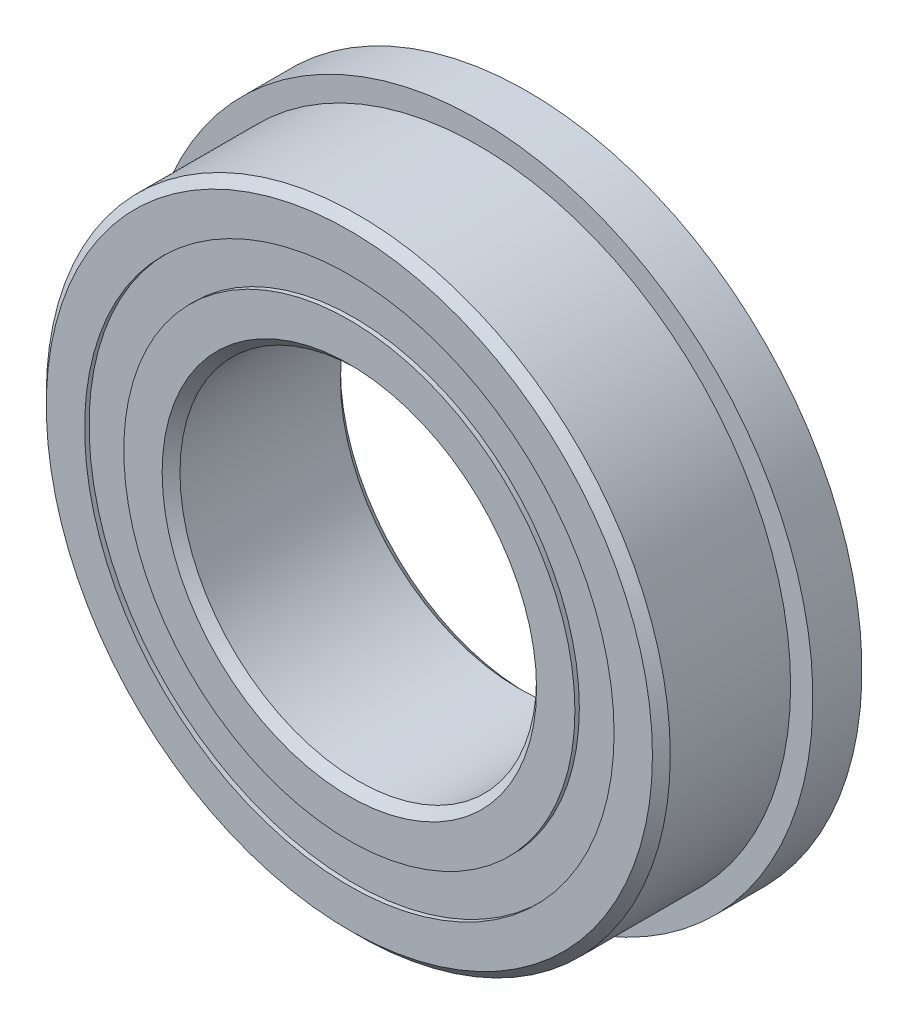
SolidWorks part; units mm, degrees
ref_plane "Front Plane" through (0, 0, 0) normal (0, 0, 1) x (1, 0, 0)
ref_plane "Top Plane" through (0, 0, 0) normal (0, 1, 0) x (1, 0, 0)
ref_plane "Right Plane" through (0, 0, 0) normal (1, 0, 0) x (0, 0, -1)
sketch "Sketch1" plane through (0, 0, 0) normal (1, 0, 0) x (0, 0, -1)
  line L0 (-2, 0) -> (2, 0) construction
  line L1 (0, 7) -> (0, -7) construction
  line L2 (1.8, 7) -> (-1.8, 7)
  line L3 (-1.8, 7) -> (-2, 6.8)
  line L4 (-2, 6.8) -> (-2, 5.9396)
  line L5 (-2, 5.9396) -> (-0.8889, 5.9396)
  line L6 (2, 5.9396) -> (0.8889, 5.9396)
  line L7 (2, 6.8) -> (2, 5.9396)
  line L8 (1.8, 7) -> (2, 6.8)
  line L9 (0, 7) -> (0, 5.5) construction
  line L10 (0, 5.5) -> (0, 4) construction
  arc A0 (-0.8889, 5.9396) -> (0.8889, 5.9396) centre (0, 5.5) cw
  point P14 (0, 4)
  dimension "D3" = 1.7778
  dimension "D1" = 45
  dimension "Width" = 4
  dimension "OD" = 14
  dimension "D2" = 0.2
  dimension "Shaft Dia" = 8
  dimension "D4" = 0.4396
revolve "Revolve1" add sketch "Sketch1" angle 360 about L0
sketch "Sketch3" plane through (0, 0, 0) normal (1, 0, 0) x (0, 0, -1)
  line L0 (-2, 5.0604) -> (-0.8889, 5.0604)
  line L1 (0, 7) -> (0, -7) construction
  line L2 (-2, 6.8) -> (-2, 5.9396) construction
  line L3 (-2, 5.0604) -> (-2, 4.2)
  line L4 (-1.8, 7) -> (-2, 6.8) construction
  line L5 (-2, 4.2) -> (-1.8, 4)
  line L6 (-1.8, 4) -> (1.8, 4)
  line L7 (1.8, 7) -> (1.8, -7) construction
  line L8 (1.8, 4) -> (2, 4.2)
  line L9 (2, -6.8) -> (2, 6.8) construction
  line L10 (2, 4.2) -> (2, 5.0604)
  line L11 (2, 5.0604) -> (0.8889, 5.0604)
  line L13 (1.8, 7) -> (2, 6.8) construction
  arc A0 (0.8889, 5.9396) -> (-0.8889, 5.9396) centre (0, 5.5) ccw construction
  arc A1 (0.8889, 5.0604) -> (-0.8889, 5.0604) centre (0, 5.5) cw
revolve "Revolve3" add sketch "Sketch3" angle 360 about L0
sketch "Sketch4" plane through (0, 0, 0) normal (1, 0, 0) x (0, 0, -1)
  line L0 (-0.9916, 5.5) -> (0.9916, 5.5)
  arc A2 (-0.9916, 5.5) -> (0.9916, 5.5) centre (0, 5.5) cw
  arc A3 (0.8889, 5.9396) -> (-0.8889, 5.9396) centre (0, 5.5) ccw construction
revolve "Revolve4" add sketch "Sketch4" angle 360 about L0
ref_axis "Axis1" through (0, 0, -2) along (0, 0, 1)
pattern_circular "CirPattern1" count 12 every 30 about axis through (0, 0, -2) along (0, 0, 1) of bodies 104
sketch "Sketch5" plane through (0, 0, 0) normal (1, 0, 0) x (0, 0, -1)
  line L0 (-2, 5.9396) -> (-0.8889, 5.9396) construction
  line L1 (-1.9, 5.9396) -> (-0.9916, 5.9396)
  line L2 (-1.9, 5.9396) -> (-1.9, 5.0604)
  line L3 (-1.9, 5.0604) -> (-0.9916, 5.0604)
  line L4 (-0.9916, 5.9396) -> (-0.9916, 5.0604)
  line L5 (-2, 5.0604) -> (-0.8889, 5.0604) construction
  line L6 (2, 5.9396) -> (0.8889, 5.9396) construction
  line L7 (1.9, 5.9396) -> (0.9916, 5.9396)
  line L8 (1.9, 5.9396) -> (1.9, 5.0604)
  line L9 (1.9, 5.0604) -> (0.9916, 5.0604)
  line L10 (0.9916, 5.9396) -> (0.9916, 5.0604)
  line L11 (2, 5.0604) -> (0.8889, 5.0604) construction
  line L12 (-1.8, 7) -> (-2, 6.8) construction
  point P18 (-1.9, 6.9)
revolve "Revolve5" add sketch "Sketch5" angle 360 about L0
sketch "Sketch6" plane through (0, 0, 0) normal (1, 0, 0) x (0, 0, -1)
  line L0 (2, 0) -> (-2, 0) construction
  line L1 (2, 5.9396) -> (0.9, 5.9396)
  line L2 (2, 5.9396) -> (2, 7.5)
  line L3 (2, 7.5) -> (0.9, 7.5)
  line L4 (0.9, 5.9396) -> (0.9, 7.5)
  dimension "Th" = 1.1
  dimension "Flange OD" = 15
revolve "Revolve6" add sketch "Sketch6" angle 360 about L0
equation "\"D2@Sketch1\" = \"Width@Sketch1\"*.05"
equation "\"D3@Sketch1\" = \"Width@Sketch1\"/2.25"
equation "\"D4@Sketch1\" = (((\"OD@Sketch1\"-\"Width@Sketch1\")/2)/3.25)/3.5"
equation "\"D2@CirPattern1\" = 360/\"Balls@CirPattern1\""
